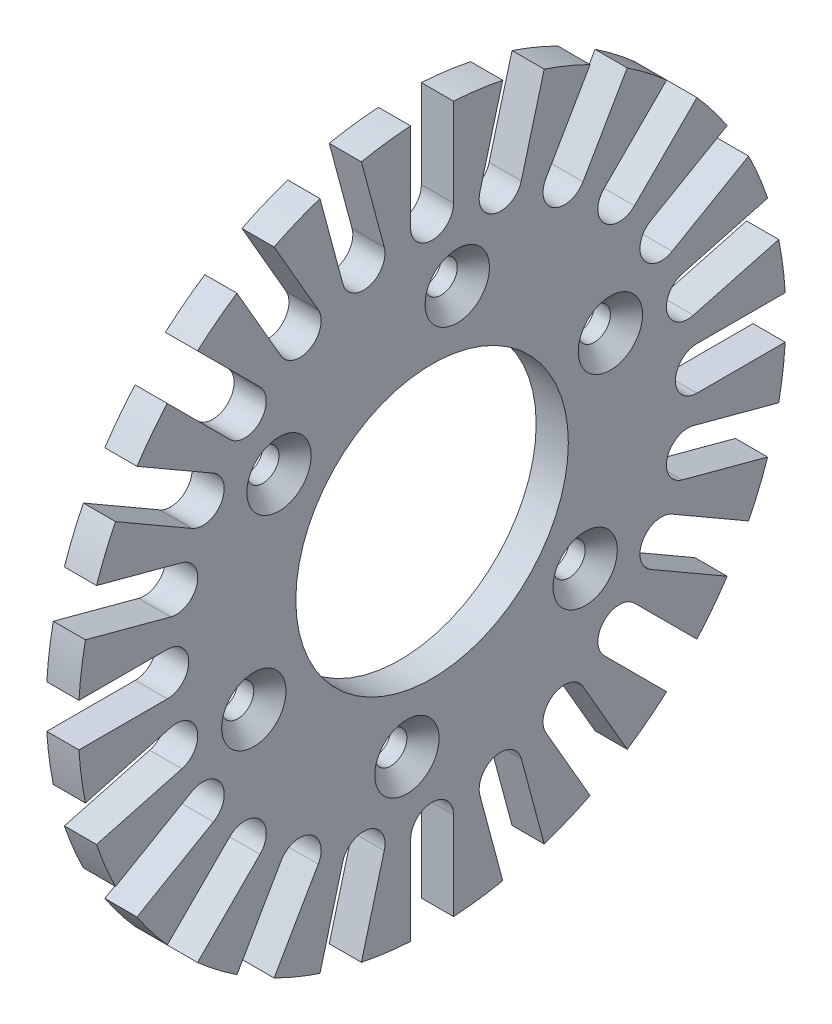
SolidWorks part; units mm, degrees
material "1060 Alloy"
ref_plane "Front Plane" through (0, 0, 0) normal (0, 0, 1) x (1, 0, 0)
ref_plane "Top Plane" through (0, 0, 0) normal (0, 1, 0) x (1, 0, 0)
ref_plane "Right Plane" through (0, 0, 0) normal (1, 0, 0) x (0, 0, -1)
sketch "Sketch1" plane through (0, 0, 0) normal (1, 0, 0) x (0, 0, -1)
  circle A0 centre (0, 0) radius 33
  dimension "D1" = 66
extrude "Boss-Extrude1" add sketch "Sketch1" along normal blind 3
sketch "Sketch3" plane through (3, 0, 0) normal (1, 0, 0) x (0, 0, -1)
  circle A0 centre (0, 0) radius 12.71
  dimension "D1" = 25.42
extrude "Cut-Extrude2" cut sketch "Sketch3" against normal up to next
sketch "Sketch4" plane through (3, 0, 0) normal (1, 0, 0) x (0, 0, -1)
  line L0 (-2, 33) -> (-2, 24.7)
  line L1 (2, 24.7) -> (2, 33)
  line L2 (2, 33) -> (-2, 33)
  arc A0 (-2, 24.7) -> (2, 24.7) centre (0, 24.7) ccw
  circle A1 centre (0, 0) radius 33 construction
  dimension "D1" = 4
  dimension "D2" = 8.3
extrude "Cut-Extrude3" cut sketch "Sketch4" against normal up to next
pattern_circular "CirPattern2" count 24 over 360 about axis through (3, 0, 0) along (1, 0, 0) of "Cut-Extrude3"
sketch "Sketch2" plane through (3, 0, 0) normal (1, 0, 0) x (0, 0, -1)
  line L0 (2.3495, 17.846) -> (0, 0) construction
  line L1 (0, 0) -> (12.71, 0) construction
  circle A0 centre (2.3495, 17.846) radius 1.5
  circle A1 centre (0, 0) radius 12.71 construction
  dimension "D1" = 3
  dimension "D2" = 18
  dimension "D3" = 82.5
extrude "Cut-Extrude1" cut sketch "Sketch2" against normal up to next
chamfer "Chamfer1" distance 1.5 angle 45 1 edges at (3, 17.846, -3.8495)
pattern_circular "CirPattern1" count 6 over 360 about axis through (3, 0, 0) along (1, 0, 0) of "Cut-Extrude1", "Chamfer1"
